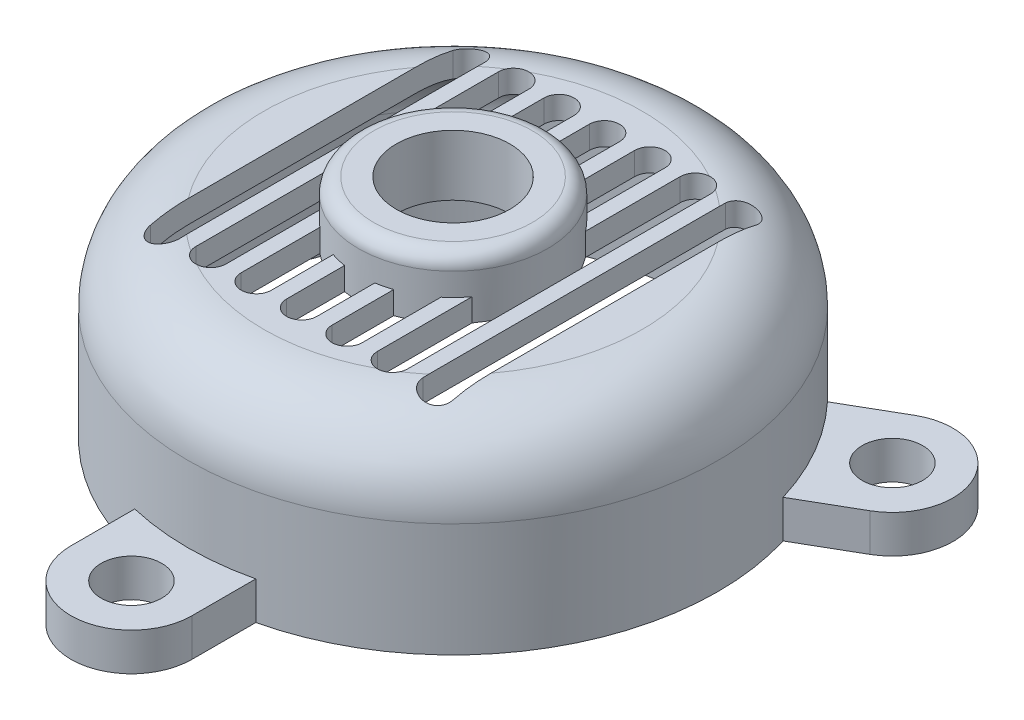
SolidWorks part; units mm, degrees
ref_plane "Front Plane" through (0, 0, 0) normal (0, 0, 1) x (1, 0, 0)
ref_plane "Top Plane" through (0, 0, 0) normal (0, 1, 0) x (1, 0, 0)
ref_plane "Right Plane" through (0, 0, 0) normal (1, 0, 0) x (0, 0, -1)
sketch "Sketch2" plane through (0, 0, 0) normal (0, 1, 0) x (1, 0, 0)
  circle A0 centre (0, 0) radius 35
  dimension "D1" = 70
extrude "Boss-Extrude1" add sketch "Sketch2" along normal blind 25
fillet "Fillet1" radius 10 1 edges at (0, 25, 35)
shell "Shell1" thickness 3 removed face at (0, 0, 35)
sketch "Sketch3" plane through (0, 0, 0) normal (0, -1, 0) x (1, 0, 0)
  line L2 (-8, 34.0735) -> (-8, 42.5)
  line L4 (8, 34.0735) -> (8, 42.5)
  circle A0 centre (0, 0) radius 35 construction
  arc A1 (8, 42.5) -> (-8, 42.5) centre (0, 42.5) ccw
  circle A2 centre (0, 42.5) radius 4
  arc A4 (8, 34.0735) -> (-8, 34.0735) centre (0, 0) ccw
  dimension "D4" = 8
  dimension "D1" = 8
  dimension "D5" = 42.5
  dimension "D2" = 8
  dimension "D3" = 16
  dimension "D6" = 42.5
extrude "Boss-Extrude2" add sketch "Sketch3" against normal blind 5
pattern_circular "CirPattern1" count 3 over 360 about axis through (0, 22, 0) along (0, -1, 0) of "Boss-Extrude2"
sketch "Sketch4" plane through (0, 25, 0) normal (0, 1, 0) x (1, 0, 0)
  line L0 (0, 20) -> (0, -20) construction
  line L1 (2, 20) -> (2, -20)
  line L2 (-2, 20) -> (-2, -20)
  line L3 (6, 20) -> (6, -20) construction
  line L4 (8, 20) -> (8, -20)
  line L5 (4, 20) -> (4, -20)
  line L6 (12, 20) -> (12, -20) construction
  line L7 (14, 20) -> (14, -20)
  line L8 (10, 20) -> (10, -20)
  line L9 (18, 20) -> (18, -20) construction
  line L10 (20, 20) -> (20, -20)
  line L11 (16, 20) -> (16, -20)
  line L12 (-6, 20) -> (-6, -20) construction
  line L13 (-4, 20) -> (-4, -20)
  line L14 (-8, 20) -> (-8, -20)
  line L15 (-12, 20) -> (-12, -20) construction
  line L16 (-10, 20) -> (-10, -20)
  line L17 (-14, 20) -> (-14, -20)
  line L18 (-18, 20) -> (-18, -20) construction
  line L19 (-16, 20) -> (-16, -20)
  line L20 (-20, 20) -> (-20, -20)
  arc A0 (2, 20) -> (-2, 20) centre (0, 20) ccw
  arc A1 (-2, -20) -> (2, -20) centre (0, -20) ccw
  arc A2 (8, 20) -> (4, 20) centre (6, 20) ccw
  arc A3 (4, -20) -> (8, -20) centre (6, -20) ccw
  arc A4 (14, 20) -> (10, 20) centre (12, 20) ccw
  arc A5 (10, -20) -> (14, -20) centre (12, -20) ccw
  arc A6 (20, 20) -> (16, 20) centre (18, 20) ccw
  arc A7 (16, -20) -> (20, -20) centre (18, -20) ccw
  arc A8 (-4, 20) -> (-8, 20) centre (-6, 20) ccw
  arc A9 (-8, -20) -> (-4, -20) centre (-6, -20) ccw
  arc A10 (-10, 20) -> (-14, 20) centre (-12, 20) ccw
  arc A11 (-14, -20) -> (-10, -20) centre (-12, -20) ccw
  arc A12 (-16, 20) -> (-20, 20) centre (-18, 20) ccw
  arc A13 (-20, -20) -> (-16, -20) centre (-18, -20) ccw
  point P2 (0, 0)
  point P7 (0, 0.0907)
  point P8 (0, 0.0907)
  point P10 (0, 0.0907)
  point P11 (0, 0.0907)
  point P15 (6, 0)
  point P22 (12, 0)
  point P29 (18, 0)
  point P36 (-6, 0)
  point P43 (-12, 0)
  point P50 (-18, 0)
  dimension "D2" = 2
  dimension "D1" = 0
  dimension "D3" = 20
  dimension "D4" = 4
  dimension "D6" = 6
  dimension "D7" = 6
  dimension "D5" = 4
extrude "Cut-Extrude1" cut sketch "Sketch4" against normal through all
ref_plane "Plane1" through (0, 30, 0) normal (0, 1, 0) x (1, 0, 0)
sketch "Sketch6" plane through (0, 30, 0) normal (0, 1, 0) x (1, 0, 0)
  circle A0 centre (0, 0) radius 12.5
  circle A1 centre (0, 0) radius 7.5
  dimension "D1" = 25
  dimension "D2" = 15
extrude "Boss-Extrude3" add sketch "Sketch6" against normal blind 8
sketch "Sketch7" plane through (0, 30, 0) normal (0, 1, 0) x (1, 0, 0)
  circle A0 centre (0, 0) radius 7.5
  dimension "D1" = 15
extrude "Cut-Extrude2" cut sketch "Sketch7" against normal through all
fillet "Fillet2" radius 2 1 edges at (0, 30, 12.5)
